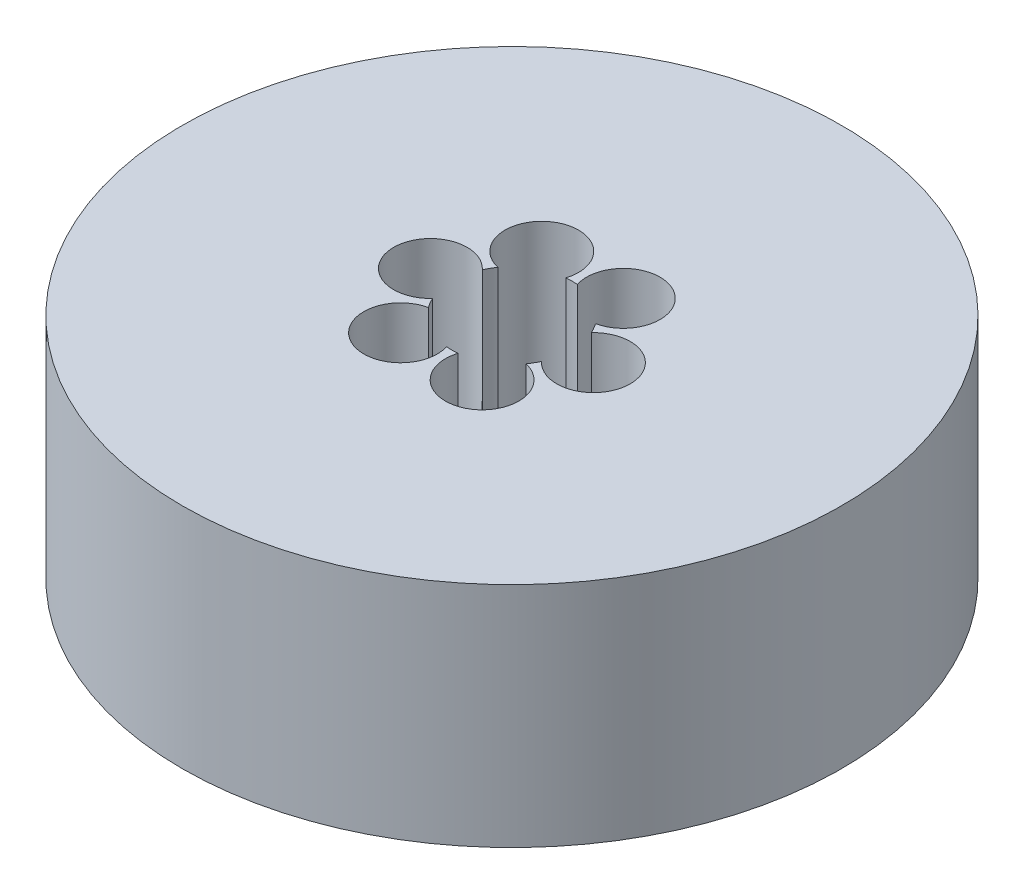
SolidWorks part; units mm, degrees
ref_plane "Front Plane" through (0, 0, 0) normal (0, 0, 1) x (1, 0, 0)
ref_plane "Top Plane" through (0, 0, 0) normal (0, 1, 0) x (1, 0, 0)
ref_plane "Right Plane" through (0, 0, 0) normal (1, 0, 0) x (0, 0, -1)
sketch "Sketch1" plane through (0, 0, 0) normal (0, 1, 0) x (1, 0, 0)
  circle A0 centre (0, 0) radius 27.5
  dimension "FLANGE_OD" = 55
extrude "Boss-Extrude1" add sketch "Sketch1" along normal blind 19
sketch "Sketch2" plane through (0, 0, 0) normal (0, 1, 0) x (1, 0, 0)
  circle A0 centre (0, 0) radius 5
  dimension "BORE_D" = 10
extrude "Cut-Extrude1" cut sketch "Sketch2" along normal through all
sketch "Sketch3" plane through (0, 19, 0) normal (0, 1, 0) x (1, 0, 0)
  circle A0 centre (0, 0) radius 6.8032 construction
  circle A1 centre (-6.8032, 0) radius 3.0664
  dimension "BOLT_D" = 6.1328
  dimension "BOLT_PCD" = 13.6065
extrude "Cut-Extrude2" cut sketch "Sketch3" against normal blind 16.2311
pattern_circular "CirPattern1" count 6 over 360 about axis through (0, 0, 0) along (0, 1, 0) of "Cut-Extrude2"
